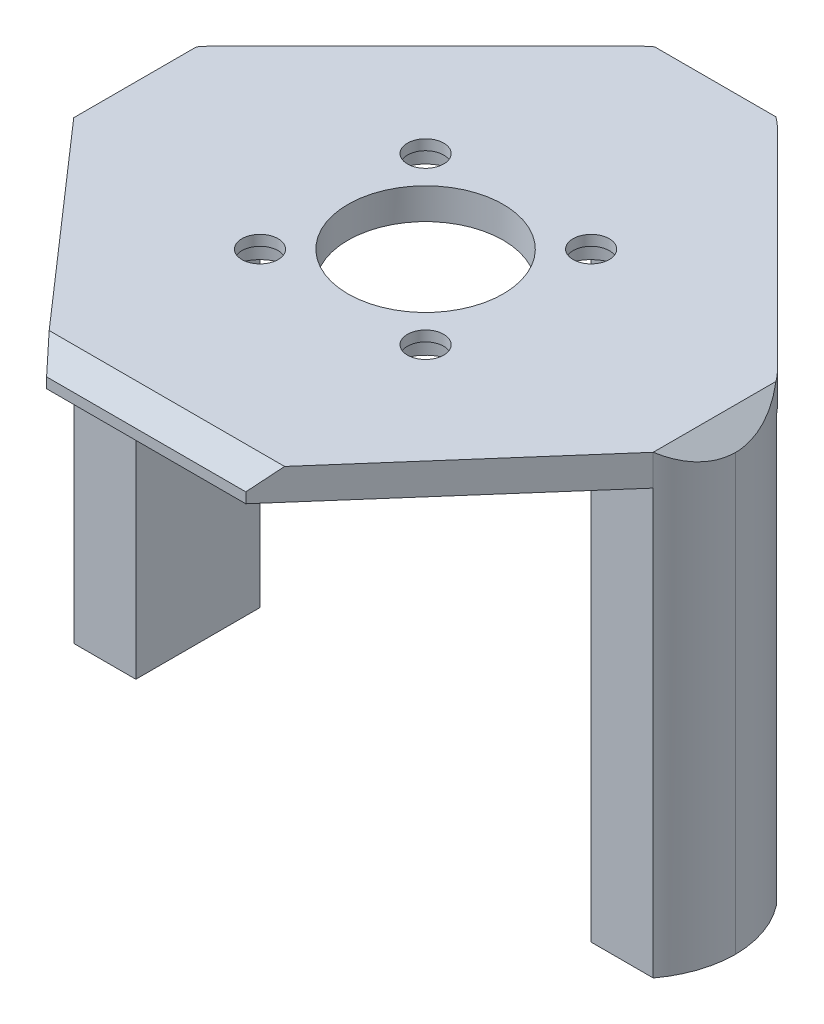
SolidWorks part; units mm, degrees
ref_plane "Front Plane" through (0, 0, 0) normal (0, 0, 1) x (1, 0, 0)
ref_plane "Top Plane" through (0, 0, 0) normal (0, 1, 0) x (1, 0, 0)
ref_plane "Right Plane" through (0, 0, 0) normal (1, 0, 0) x (0, 0, -1)
sketch "Sketch1" plane through (0, 0, 0) normal (0, 1, 0) x (1, 0, 0)
  line L1 (-30, -30) -> (30, -30)
  line L2 (-30, -30) -> (-30, 30)
  line L3 (-30, 30) -> (30, 30)
  line L4 (30, -30) -> (30, 30)
  line L5 (-30, -30) -> (30, 30) construction
  line L6 (-30, 30) -> (30, -30) construction
  point P0 (0, 0)
  dimension "D1" = 60
  dimension "D2" = 60
extrude "Boss-Extrude1" add sketch "Sketch1" along normal blind 3
sketch "Sketch4" plane through (0, 0, 0) normal (0, -1, 0) x (1, 0, 0)
  line L0 (-22, 6) -> (-22, -6)
  line L1 (-22, 6) -> (-30, 6)
  line L2 (30, -30) -> (-30, -30) construction
  line L3 (-30, 0) -> (30, 0) construction
  line L4 (-6, -22) -> (6, -22)
  line L5 (-6, -22) -> (-6, -30)
  line L6 (-6, -30) -> (6, -30)
  line L7 (6, -22) -> (6, -30)
  line L8 (-6, -22) -> (6, -30) construction
  line L9 (-6, -30) -> (6, -22) construction
  line L10 (-30, -30) -> (-30, 30) construction
  line L11 (30, 30) -> (30, -30) construction
  line L12 (-30, 6) -> (-30, -6)
  line L13 (-22, -6) -> (-30, -6)
  line L18 (-22, 6) -> (-30, -6) construction
  line L19 (0, 0) -> (0, -30) construction
  line L20 (-30, 6) -> (-22, -6) construction
  line L27 (22, -6) -> (22, 6)
  line L28 (22, -6) -> (30, -6)
  line L29 (30, -6) -> (30, 6)
  line L30 (22, 6) -> (30, 6)
  line L31 (22, -6) -> (30, 6) construction
  line L32 (30, -6) -> (22, 6) construction
  arc A0 (0, -23) -> (0, -30) centre (0, -26.5) ccw construction
  arc A1 (0, -30) -> (0, -23) centre (0, -26.5) ccw construction
  arc A2 (-23, 0) -> (-30, 0) centre (-26.5, 0) ccw construction
  arc A3 (-30, 0) -> (-23, 0) centre (-26.5, 0) ccw construction
  arc A6 (23, 0) -> (30, 0) centre (26.5, 0) ccw construction
  arc A7 (30, 0) -> (23, 0) centre (26.5, 0) ccw construction
  point P7 (0, -26)
  point P21 (-26, 0)
  point P38 (26, 0)
  point P44 (0, 0)
  dimension "D1" = 7
  dimension "D2" = 8
  dimension "D3" = 12
extrude "Boss-Extrude3" add sketch "Sketch4" along normal blind 41
sketch "Sketch5" plane through (0, -41, 0) normal (0, -1, 0) x (1, 0, 0)
  circle A0 centre (0, -26.5) radius 2
  circle A2 centre (-26.5, 0) radius 2
  circle A4 centre (26.5, 0) radius 2
  circle A5 centre (0, 26.5) radius 2 [skipped]
  dimension "D1" = 4
extrude "Cut-Extrude2" cut sketch "Sketch5" against normal blind 6
sketch "Sketch7" plane through (0, 0, 0) normal (0, -1, 0) x (1, 0, 0)
  line L0 (-30, -6) -> (-6, -30)
  line L1 (-6, -30) -> (-30, -30)
  line L2 (-30, -30) -> (-30, -6)
  line L3 (30, -6) -> (6, -30)
  line L4 (6, -30) -> (30, -30)
  line L5 (30, -30) -> (30, -6)
sketch "Sketch8" plane through (0, 3, 0) normal (0, 1, 0) x (1, 0, 0)
  circle A0 centre (0, 0) radius 7.5
  point P0 (0, 0)
  dimension "D1" = 15
extrude "Cut-Extrude4" cut sketch "Sketch8" against normal blind 6
extrude "Cut-Extrude5" cut sketch "Sketch7" against normal blind 6
sketch "Sketch10" plane through (0, 0, 0) normal (0, -1, 0) x (1, 0, 0)
  line L0 (0, -30) -> (0, 30) construction
  line L1 (-6, -30) -> (6, -30) construction
  line L2 (-30, 30) -> (30, 30) construction
  line L3 (-9, 30) -> (0, 30) construction
  line L6 (0, 30) -> (9, 30) construction
  line L7 (-9, 30) -> (-30, 6)
  line L8 (-30, 6) -> (-30, 30)
  line L9 (-30, 30) -> (-9, 30)
  line L10 (9, 30) -> (30, 6)
  line L11 (30, 6) -> (30, 30)
  line L12 (30, 30) -> (9, 30)
  point P6 (0, 22.4368)
  dimension "D1" = 18
extrude "Cut-Extrude6" cut sketch "Sketch10" against normal blind 6
sketch "Sketch11" plane through (0, 0, 0) normal (0, -1, 0) x (1, 0, 0)
  line L0 (-9, 30) -> (9, 30) construction
  line L5 (-11.625, 30) -> (11.625, 30)
  line L6 (-11.625, 30) -> (-11.625, 27)
  line L7 (-11.625, 27) -> (11.625, 27)
  line L8 (11.625, 30) -> (11.625, 27)
  line L9 (9, 30) -> (30, 6) construction
  line L10 (-30, 6) -> (-9, 30) construction
  dimension "D1" = 3
extrude "Cut-Extrude7" cut sketch "Sketch11" against normal blind 6
sketch "Sketch12" plane through (0, 0, 0) normal (0, -1, 0) x (1, 0, 0)
  line L0 (-8, 8) -> (0, 0) construction
  line L1 (-8, -8) -> (8, -8) construction
  line L2 (-8, -8) -> (-8, 8) construction
  line L3 (-8, 8) -> (8, 8) construction
  line L4 (8, -8) -> (8, 8) construction
  line L5 (-8, -8) -> (0, 0) construction
  line L6 (0, 0) -> (8, -8) construction
  line L7 (0, 0) -> (8, 8) construction
  circle A0 centre (-8, 8) radius 3
  circle A4 centre (8, 8) radius 3
  circle A5 centre (8, -8) radius 3
  circle A6 centre (-8, -8) radius 3
  point P0 (0, 0)
  point P17 (0.5, 0)
  point P18 (0, 0)
  dimension "D2" = 6
  dimension "D1" = 16
  dimension "D3" = 4
extrude "Cut-Extrude8" cut sketch "Sketch12" against normal blind 2
sketch "Sketch13" plane through (0, 3, 0) normal (0, 1, 0) x (1, 0, 0)
  line L0 (-8, 8) -> (0, 0) construction
  line L1 (-8, -8) -> (8, -8) construction
  line L2 (-8, -8) -> (-8, 8) construction
  line L3 (-8, 8) -> (8, 8) construction
  line L4 (8, -8) -> (8, 8) construction
  line L5 (-8, -8) -> (0, 0) construction
  line L6 (0, 0) -> (8, -8) construction
  line L7 (0, 0) -> (8, 8) construction
  circle A0 centre (-8, 8) radius 1.75
  circle A1 centre (8, 8) radius 1.75
  circle A2 centre (8, -8) radius 1.75
  circle A3 centre (-8, -8) radius 1.75
  point P0 (0, 0)
  point P17 (0, 0)
  dimension "D2" = 3.5
  dimension "D1" = 16
  dimension "D3" = 4
extrude "Cut-Extrude9" cut sketch "Sketch13" against normal blind 1
chamfer "Chamfer1" distance 2 angle 45 3 edges at (30, 3, 0) (-30, 3, 0) (0, 3, -30)
chamfer "Chamfer2" distance 2 angle 45 1 edges at (0, 3, 27)
chamfer "Chamfer3" distance 2 angle 45 6 edges at (30, -20.5, 6) (-30, -20.5, 6) (-30, -20.5, -6) (-6, -20.5, -30) (30, -20.5, -6) (6, -20.5, -30)
sketch "Sketch14" plane through (0, 0, 0) normal (0, -1, 0) x (1, 0, 0)
  line L0 (-30, -4) -> (-4, -30)
  line L1 (-4, -30) -> (-6, -30)
  line L2 (-6, -30) -> (-30, -6)
  line L3 (-6, -30) -> (-30, -6) construction
  line L4 (-30, -6) -> (-30, -4) construction
  line L5 (-30, -6) -> (-30, -4)
  line L6 (4, -30) -> (30, -4)
  line L7 (30, -4) -> (30, -6)
  line L8 (30, -6) -> (6, -30)
  line L9 (6, -30) -> (4, -30)
extrude "Cut-Extrude10" cut sketch "Sketch14" against normal blind 10
fillet "Fillet1" radius 10 6 edges at (-4, -20, -30) (4, -20, -30) (-30, -20.5, 4) (-30, -20, -4) (30, -20.5, 4) (30, -20, -4)
sketch "Sketch15" plane through (0, 0, 0) normal (0, -1, 0) x (1, 0, 0)
  line L0 (-30, 6) -> (30, 6) construction
  line L1 (-29.4466, -3.1385) -> (11.625, 27) construction
  line L2 (-29.9997, 0.0711) -> (29.9997, 0.0711) construction
  arc A0 (-29.9997, 0.0711) -> (-27.8914, -6) centre (-20, 0.1421) ccw construction
sketch "Sketch16" plane through (0, 0, 0) normal (0, -1, 0) x (1, 0, 0)
  line L0 (-28, 6) -> (-9.625, 27)
  line L1 (28, 6) -> (9.625, 27)
  line L2 (-9.625, 27) -> (-11.625, 27)
  line L16 (6, -22) -> (6, -27.8914)
  line L17 (6.9289, -27.0711) -> (27.0711, -6.9289)
  line L18 (27.8914, -6) -> (22, -6)
  line L19 (22, -6) -> (22, 6)
  line L20 (22, 6) -> (28, 6)
  line L21 (30, 0.1421) -> (30, 6)
  line L22 (30, 6) -> (11.625, 27)
  line L23 (11.625, 27) -> (-11.625, 27)
  line L24 (-11.625, 27) -> (-30, 6)
  line L25 (-30, 6) -> (-30, 0.1421)
  line L26 (-28, 6) -> (-22, 6)
  line L27 (-22, 6) -> (-22, -6)
  line L28 (-22, -6) -> (-27.8914, -6)
  line L29 (-27.0711, -6.9289) -> (-6.9289, -27.0711)
  line L30 (-6, -27.8914) -> (-6, -22)
  line L31 (-6, -22) -> (6, -22)
  line L37 (30, 0.1421) -> (30, 6)
  line L38 (30, 6) -> (11.625, 27)
  line L39 (11.625, 27) -> (9.625, 27)
  line L40 (-11.625, 27) -> (-30, 6)
  line L41 (-30, 6) -> (-30, 0.1421)
  arc A8 (6, -27.8914) -> (6.9289, -27.0711) centre (-0.1421, -20) ccw
  arc A9 (27.0711, -6.9289) -> (27.8914, -6) centre (20, 0.1421) ccw
  arc A10 (29.9997, 0.0711) -> (28, 6) centre (20, 0) ccw
  arc A11 (29.9997, 0.0711) -> (30, 0.1421) centre (20, 0.1421) ccw
  arc A12 (-30, 0.1421) -> (-29.9997, 0.0711) centre (-20, 0.1421) ccw
  arc A13 (-28, 6) -> (-29.9997, 0.0711) centre (-20, 0) ccw
  arc A14 (-27.8914, -6) -> (-27.0711, -6.9289) centre (-20, 0.1421) ccw
  arc A15 (-6.9289, -27.0711) -> (-6, -27.8914) centre (0.1421, -20) ccw
  arc A18 (29.9997, 0.0711) -> (28, 6) centre (20, 0) ccw
  arc A19 (29.9997, 0.0711) -> (30, 0.1421) centre (20, 0.1421) ccw
  arc A20 (-30, 0.1421) -> (-29.9997, 0.0711) centre (-20, 0.1421) ccw
  arc A21 (-28, 6) -> (-29.9997, 0.0711) centre (-20, 0) ccw
  dimension "D1" = 0
extrude "Cut-Extrude11" cut sketch "Sketch16" against normal through all
